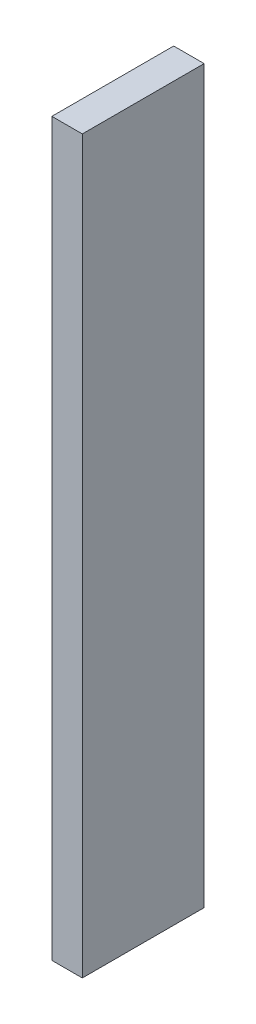
SolidWorks part; units mm, degrees
ref_plane "Front Plane" through (0, 0, 0) normal (0, 0, 1) x (1, 0, 0)
ref_plane "Top Plane" through (0, 0, 0) normal (0, 1, 0) x (1, 0, 0)
ref_plane "Right Plane" through (0, 0, 0) normal (1, 0, 0) x (0, 0, -1)
sketch "Sketch1" plane through (0, 0, 0) normal (0, 1, 0) x (1, 0, 0)
  line L1 (0, 0) -> (3.175, 0)
  line L2 (0, 0) -> (0, 12.7)
  line L3 (0, 12.7) -> (3.175, 12.7)
  line L4 (3.175, 0) -> (3.175, 12.7)
  dimension "D1" = 3.175
  dimension "D2" = 12.7
extrude "Boss-Extrude1" add sketch "Sketch1" along normal blind 76.2
equation "\"D1@Sketch1\"=1/8"
